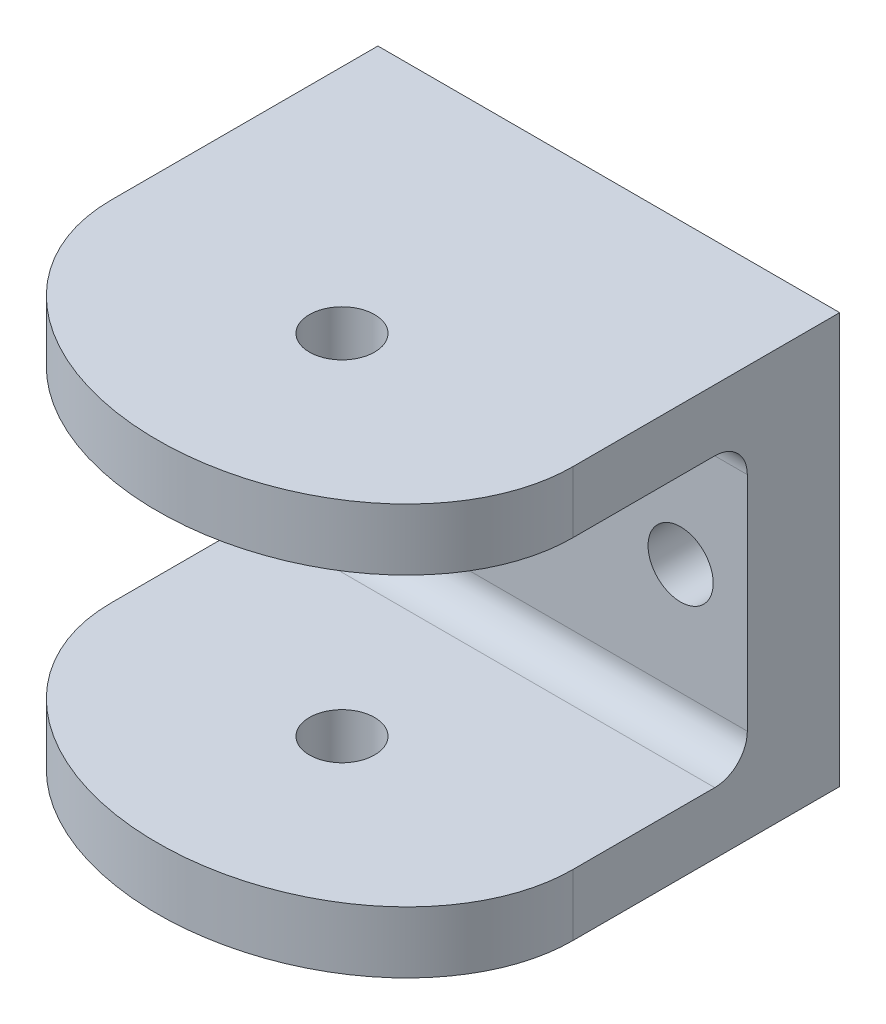
SolidWorks part; units mm, degrees
ref_plane "Front Plane" through (0, 0, 0) normal (0, 0, 1) x (1, 0, 0)
ref_plane "Top Plane" through (0, 0, 0) normal (0, 1, 0) x (1, 0, 0)
ref_plane "Right Plane" through (0, 0, 0) normal (1, 0, 0) x (0, 0, -1)
sketch "Sketch1" plane through (0, 0, 0) normal (0, 0, 1) x (1, 0, 0)
  line L0 (0, 0) -> (-16, 0) construction
  line L1 (-22.5, -20) -> (22.5, -20)
  line L2 (-22.5, -20) -> (-22.5, 20)
  line L3 (-22.5, 20) -> (22.5, 20)
  line L4 (22.5, -20) -> (22.5, 20)
  line L5 (-22.5, -20) -> (22.5, 20) construction
  line L6 (-22.5, 20) -> (22.5, -20) construction
  line L7 (0, 0) -> (16, 0) construction
  circle A0 centre (16, 0) radius 3.175
  circle A1 centre (-16, 0) radius 3.175
  point P0 (0, 0)
  dimension "D4" = 6.35
  dimension "D1" = 45
  dimension "D2" = 40
  dimension "D3" = 32
extrude "Boss-Extrude1" add sketch "Sketch1" along normal blind 9
sketch "Sketch2" plane through (0, 0, 9) normal (0, 0, 1) x (1, 0, 0)
  line L1 (-22.5, 20) -> (22.5, 20)
  line L2 (-22.5, 20) -> (-22.5, 14)
  line L3 (-22.5, 14) -> (22.5, 14)
  line L4 (22.5, -20) -> (22.5, 20)
  line L5 (22.5, 20) -> (-22.5, 20)
  line L6 (-22.5, 20) -> (-22.5, -20)
  line L7 (-22.5, -20) -> (22.5, -20)
  line L8 (22.5, -20) -> (22.5, 20) construction
  line L9 (22.5, 20) -> (-22.5, 20) construction
  line L10 (-22.5, 20) -> (-22.5, -20) construction
  line L11 (-22.5, -20) -> (22.5, -20) construction
  line L12 (22.5, 20) -> (22.5, 14)
  line L13 (22.5, -20) -> (-22.5, -20)
  line L14 (22.5, -20) -> (22.5, -14)
  line L15 (22.5, -14) -> (-22.5, -14)
  line L16 (-22.5, -20) -> (-22.5, -14)
  dimension "D2" = 6
  dimension "D3" = 6
  dimension "D1" = 0
extrude "Boss-Extrude2" add sketch "Sketch2" along normal blind 35
fillet "Fillet1" radius 3.175 2 edges at (0, 14, 9) (0, -14, 9)
sketch "Sketch3" plane through (0, 20, 0) normal (0, 1, 0) x (1, 0, 0)
  line L0 (22.5, -9) -> (-22.5, -9) construction
  line L1 (22.5, -9) -> (-22.5, -9) construction
  line L2 (22.5, -44) -> (22.5, 0) construction
  line L3 (22.5, -44) -> (22.5, -26)
  line L4 (-22.5, -44) -> (-22.5, 0) construction
  line L6 (-22.5, -44) -> (-22.5, -26)
  line L7 (22.5, -44) -> (-22.5, -44)
  line L8 (22.5, 0) -> (-22.5, 0) construction
  circle A0 centre (0, -26) radius 3.175
  ellipse E0 centre (0, -26) end of major axis (-22.5, -26) minor radius 18 (-22.5, -26) -> (7.3951, -9) ccw
  point P4 (0, -9)
  line M6 (-22.5, 0) -> (-22.5, -44)
  line M7 (-22.5, -44) -> (22.5, -44)
  line M8 (22.5, -44) -> (22.5, 0)
  dimension "D1" = 6.35
  dimension "D2" = 26
  dimension "D3" = 22.5
  dimension "D4" = 0
  dimension "D5" = 18
extrude "Cut-Extrude1" cut sketch "Sketch3" against normal through all contours M6 M7 | L7 M8 | A0 region at (17.4767, 20, 39.9774) region at (-17.4742, 20, 39.9794) region at (0, 20, 26)
ref_point "Point4"
ref_point "Point6"
ref_point "Point8"
ref_point "Point12"
sketch "Sketch4" plane through (0, 0, 0) normal (0, 1, 0) x (1, 0, 0)
  point P0 (0, -26)
